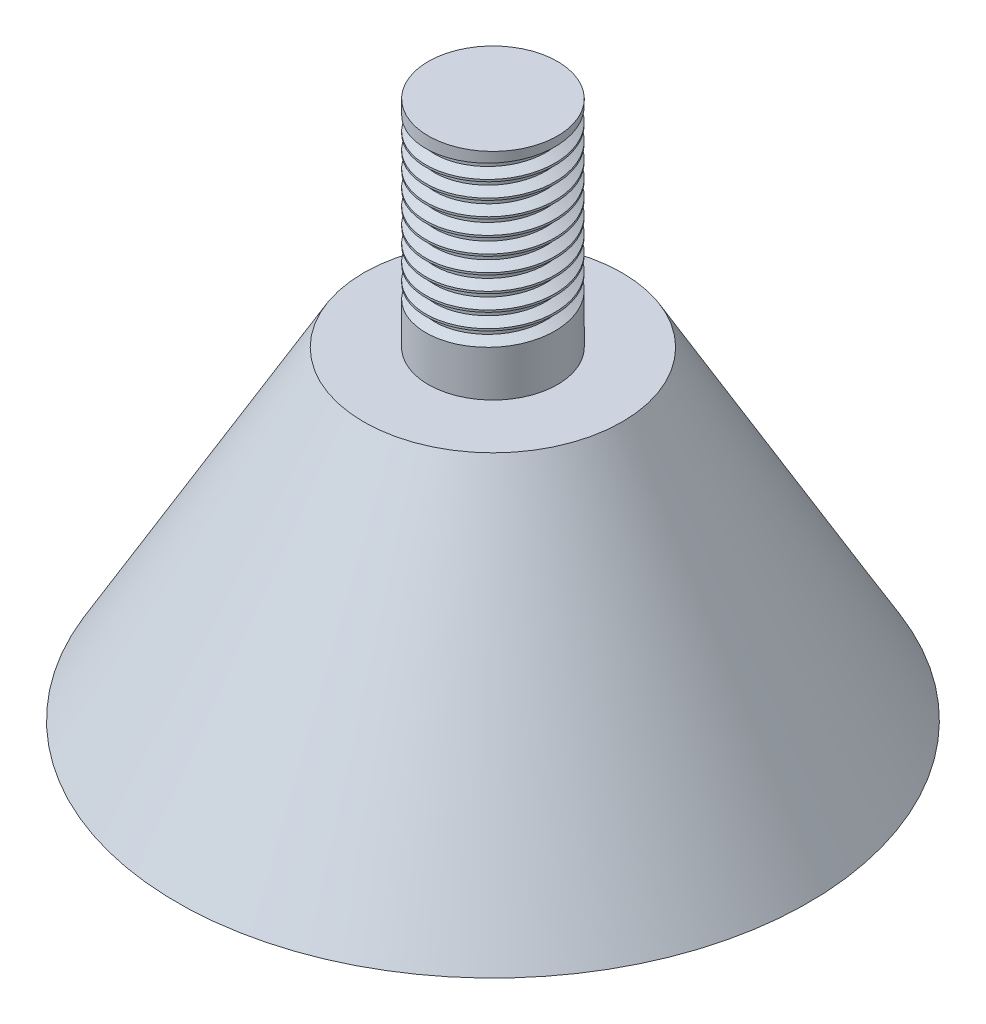
SolidWorks part; units mm, degrees
ref_plane "Ön Düzlem" through (0, 0, 0) normal (0, 0, 1) x (1, 0, 0)
ref_plane "Üst Düzlem" through (0, 0, 0) normal (0, 1, 0) x (1, 0, 0)
ref_plane "Sağ Düzlem" through (0, 0, 0) normal (1, 0, 0) x (0, 0, -1)
sketch "Çizim1" plane through (0, 0, 0) normal (0, 0, 1) x (1, 0, 0)
  line L0 (0, 0) -> (0, 42.097) construction
  line L1 (0, 0) -> (76.0466, 0) construction
  line L2 (0, 0) -> (0, 30)
  line L3 (0, 30) -> (10, 30)
  line L4 (10, 30) -> (27.3205, 0)
  line L5 (27.3205, 0) -> (0, 0)
  dimension "D1" = 30
  dimension "D2" = 60
  dimension "D3" = 10
revolve "Döndür1" add sketch "Çizim1" angle 360 about L2
sketch "Çizim2" plane through (0, 0, 0) normal (0, 0, 1) x (1, 0, 0)
  line L3 (10, 30) -> (12, 30)
  line L4 (12, 30) -> (29.3205, 0)
  line L5 (29.3205, 0) -> (27.3205, 0)
  line L6 (10, 30) -> (27.3205, 0)
  line L7 (27.3205, 0) -> (10, 30) construction
  line L8 (0, 0) -> (0, 35.0246) construction
  line L9 (-27.3205, 0) -> (27.3205, 0) construction
  dimension "D1" = 2
  dimension "D2" = 120
revolve "Döndür2" add sketch "Çizim2" angle 360 about L8
sketch "Çizim3" plane through (0, 30, 0) normal (0, 1, 0) x (1, 0, 0)
  circle A0 centre (0, 0) radius 6
  dimension "D1" = 12
extrude "Yükseklik-Ekstrüzyon1" add sketch "Çizim3" along normal blind 20
thread "Diş1" pitch 1.5 method cut profile "Diş Profili1" start angle 0, offset 0, length 15, pitch 1.5, diameter 12
ref_plane "Düzlem1" through (-6, 50, 0) normal (0, 0, 1) x (-1, 0, 0)
sketch "Diş Profili1" plane through (-6, 50, 0) normal (0, 0, 1) x (-1, 0, 0)
  line L0 (0, 0) -> (0, 1.5) construction
  line L11 (0, 0) -> (0, 1.3125)
  line L12 (0, 1.3125) -> (-0.8119, 0.8437)
  line L13 (-0.8119, 0.8437) -> (-0.8119, 0.4687)
  line L15 (-0.8119, 0.4687) -> (0, 0)
  line L17 (-0.8119, 0.6562) -> (0, 0.6562) construction
  point P2 (0, 0)
  dimension "Pitch" = 1.5
  dimension "Profile_Angle" = 60
  dimension "Profile_Land" = 0.375
  dimension "Profile_Height" = 0.8119
